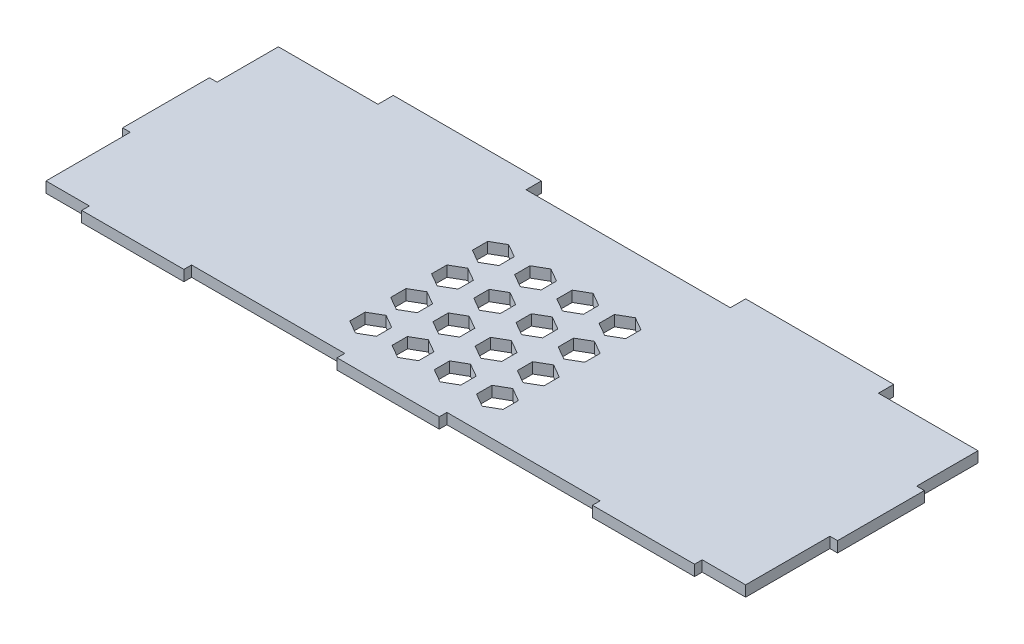
SolidWorks part; units mm, degrees
ref_plane "Front Plane" through (0, 0, 0) normal (0, 0, 1) x (1, 0, 0)
ref_plane "Top Plane" through (0, 0, 0) normal (0, 1, 0) x (1, 0, 0)
ref_plane "Right Plane" through (0, 0, 0) normal (1, 0, 0) x (0, 0, -1)
sketch "Sketch2" plane through (0, 0, 0) normal (0, 1, 0) x (1, 0, 0)
  line L5 (-70, 23.5) -> (-49, 23.5)
  line L6 (70, -23.5) -> (-70, -23.5)
  line L15 (70, -23.5) -> (70, 23.5)
  line L17 (-70, -23.5) -> (-70, 23.5)
  line L18 (70, -23.5) -> (-70, 23.5) construction
  line L19 (70, 23.5) -> (-70, -23.5) construction
  line L20 (-49, 23.5) -> (-49, 26.5)
  line L21 (-49, 26.5) -> (-20, 26.5)
  line L22 (-20, 26.5) -> (-20, 23.5)
  line L24 (20, 23.5) -> (20, 26.5)
  line L25 (20, 26.5) -> (49, 26.5)
  line L26 (49, 26.5) -> (49, 23.5)
  line L27 (49, 23.5) -> (70, 23.5)
  line L28 (-20, 23.5) -> (20, 23.5)
  point P0 (0, 0)
  dimension "D1" = 140
  dimension "D2" = 47
  dimension "D3" = 140
  dimension "D4" = 21
  dimension "D5" = 29
  dimension "D6" = 29
  dimension "D7" = 21
  dimension "D8" = 40
  dimension "D9" = 3
  dimension "D10" = 3
  dimension "D11" = 47
extrude "Boss-Extrude1" add sketch "Sketch2" along normal blind 2.1
sketch "Sketch5" plane through (0, 2.1, 0) normal (0, 1, 0) x (1, 0, 0)
  line L0 (-4.134, -11.5) -> (-6.7321, -13)
  line L1 (-12.4019, -11.5) -> (-15, -13)
  line L2 (-15, -13) -> (-15, -16)
  line L3 (-15, -16) -> (-12.4019, -17.5)
  line L4 (-12.4019, -17.5) -> (-9.8038, -16)
  line L5 (-9.8038, -16) -> (-9.8038, -13)
  line L6 (-9.8038, -13) -> (-12.4019, -11.5)
  line L7 (-6.7321, -13) -> (-6.7321, -16)
  line L8 (-6.7321, -16) -> (-4.134, -17.5)
  line L9 (-4.134, -17.5) -> (-1.5359, -16)
  line L10 (-1.5359, -16) -> (-1.5359, -13)
  line L11 (-1.5359, -13) -> (-4.134, -11.5)
  line L12 (4.134, -11.5) -> (1.5359, -13)
  line L13 (1.5359, -13) -> (1.5359, -16)
  line L14 (1.5359, -16) -> (4.134, -17.5)
  line L15 (4.134, -17.5) -> (6.7321, -16)
  line L16 (6.7321, -16) -> (6.7321, -13)
  line L17 (6.7321, -13) -> (4.134, -11.5)
  line L18 (12.4019, -11.5) -> (9.8038, -13)
  line L19 (9.8038, -13) -> (9.8038, -16)
  line L20 (9.8038, -16) -> (12.4019, -17.5)
  line L21 (12.4019, -17.5) -> (15, -16)
  line L22 (15, -16) -> (15, -13)
  line L23 (15, -13) -> (12.4019, -11.5)
  line L24 (-4.134, -3.5) -> (-6.7321, -5)
  line L25 (-6.7321, -5) -> (-6.7321, -8)
  line L26 (-6.7321, -8) -> (-4.134, -9.5)
  line L27 (-4.134, -9.5) -> (-1.5359, -8)
  line L28 (-1.5359, -8) -> (-1.5359, -5)
  line L29 (-1.5359, -5) -> (-4.134, -3.5)
  line L30 (4.134, -3.5) -> (1.5359, -5)
  line L31 (1.5359, -5) -> (1.5359, -8)
  line L32 (1.5359, -8) -> (4.134, -9.5)
  line L33 (4.134, -9.5) -> (6.7321, -8)
  line L34 (6.7321, -8) -> (6.7321, -5)
  line L35 (6.7321, -5) -> (4.134, -3.5)
  line L36 (12.4019, -3.5) -> (9.8038, -5)
  line L37 (9.8038, -5) -> (9.8038, -8)
  line L38 (9.8038, -8) -> (12.4019, -9.5)
  line L39 (12.4019, -9.5) -> (15, -8)
  line L40 (15, -8) -> (15, -5)
  line L41 (15, -5) -> (12.4019, -3.5)
  line L42 (-4.134, 4.5) -> (-6.7321, 3)
  line L43 (-6.7321, 3) -> (-6.7321, 0)
  line L44 (-6.7321, 0) -> (-4.134, -1.5)
  line L45 (-4.134, -1.5) -> (-1.5359, 0)
  line L46 (-1.5359, 0) -> (-1.5359, 3)
  line L47 (-1.5359, 3) -> (-4.134, 4.5)
  line L48 (4.134, 4.5) -> (1.5359, 3)
  line L49 (1.5359, 3) -> (1.5359, 0)
  line L50 (1.5359, 0) -> (4.134, -1.5)
  line L51 (4.134, -1.5) -> (6.7321, 0)
  line L52 (6.7321, 0) -> (6.7321, 3)
  line L53 (6.7321, 3) -> (4.134, 4.5)
  line L54 (12.4019, 4.5) -> (9.8038, 3)
  line L55 (9.8038, 3) -> (9.8038, 0)
  line L56 (9.8038, 0) -> (12.4019, -1.5)
  line L57 (12.4019, -1.5) -> (15, 0)
  line L58 (15, 0) -> (15, 3)
  line L59 (15, 3) -> (12.4019, 4.5)
  line L60 (-4.134, 12.5) -> (-6.7321, 11)
  line L61 (-6.7321, 11) -> (-6.7321, 8)
  line L62 (-6.7321, 8) -> (-4.134, 6.5)
  line L63 (-4.134, 6.5) -> (-1.5359, 8)
  line L64 (-1.5359, 8) -> (-1.5359, 11)
  line L65 (-1.5359, 11) -> (-4.134, 12.5)
  line L66 (4.134, 12.5) -> (1.5359, 11)
  line L67 (1.5359, 11) -> (1.5359, 8)
  line L68 (1.5359, 8) -> (4.134, 6.5)
  line L69 (4.134, 6.5) -> (6.7321, 8)
  line L70 (6.7321, 8) -> (6.7321, 11)
  line L71 (6.7321, 11) -> (4.134, 12.5)
  line L72 (12.4019, 12.5) -> (9.8038, 11)
  line L73 (9.8038, 11) -> (9.8038, 8)
  line L74 (9.8038, 8) -> (12.4019, 6.5)
  line L75 (12.4019, 6.5) -> (15, 8)
  line L76 (15, 8) -> (15, 11)
  line L77 (15, 11) -> (12.4019, 12.5)
  line L78 (-12.4019, -3.5) -> (-15, -5)
  line L79 (-15, -5) -> (-15, -8)
  line L80 (-15, -8) -> (-12.4019, -9.5)
  line L81 (-12.4019, -9.5) -> (-9.8038, -8)
  line L82 (-9.8038, -8) -> (-9.8038, -5)
  line L83 (-9.8038, -5) -> (-12.4019, -3.5)
  line L84 (-12.4019, 4.5) -> (-15, 3)
  line L85 (-15, 3) -> (-15, 0)
  line L86 (-15, 0) -> (-12.4019, -1.5)
  line L87 (-12.4019, -1.5) -> (-9.8038, 0)
  line L88 (-9.8038, 0) -> (-9.8038, 3)
  line L89 (-9.8038, 3) -> (-12.4019, 4.5)
  line L90 (-12.4019, 12.5) -> (-15, 11)
  line L91 (-15, 11) -> (-15, 8)
  line L92 (-15, 8) -> (-12.4019, 6.5)
  line L93 (-12.4019, 6.5) -> (-9.8038, 8)
  line L94 (-9.8038, 8) -> (-9.8038, 11)
  line L95 (-9.8038, 11) -> (-12.4019, 12.5)
  line L99 (20, 23.5) -> (-20, 23.5) construction
  line L100 (-70, 23.5) -> (-70, -23.5) construction
  line L101 (70, -23.5) -> (70, 23.5) construction
  circle A0 centre (-12.4019, -14.5) radius 2.5981 construction
  dimension "D1" = 3
  dimension "D4" = 55
  dimension "D5" = 55
  dimension "D6" = 14.5
  dimension "D7" = 8
  dimension "D8" = 11
  dimension "D2" = 4
  dimension "D3" = 4
extrude "Cut-Extrude1" cut sketch "Sketch5" against normal through all
sketch "Sketch6" plane through (0, 2.1, 0) normal (0, 1, 0) x (1, 0, 0)
  line L0 (70, 23.5) -> (68.5, 23.5)
  line L1 (70, 23.5) -> (49, 23.5) construction
  line L2 (68.5, 23.5) -> (68.5, 11.5)
  line L4 (70, -23.5) -> (70, 23.5) construction
  line L9 (70, 11.5) -> (70, 23.5)
  line L10 (68.5, -5.5) -> (68.5, -23.5)
  line L11 (-70, -23.5) -> (70, -23.5) construction
  line L12 (68.5, -23.5) -> (70, -23.5)
  line L13 (70, -23.5) -> (70, -5.5)
  line L14 (70, -23.5) -> (70, -22)
  line L15 (70, -22) -> (60, -22)
  line L16 (60, -22) -> (60, -23.5)
  line L17 (60, -23.5) -> (70, -23.5)
  line L18 (40, -23.5) -> (40, -22)
  line L19 (40, -22) -> (10, -22)
  line L20 (10, -22) -> (10, -23.5)
  line L21 (10, -23.5) -> (40, -23.5)
  line L22 (-10, -23.5) -> (-10, -22)
  line L23 (-10, -22) -> (-40, -22)
  line L24 (-40, -22) -> (-40, -23.5)
  line L25 (-40, -23.5) -> (-10, -23.5)
  line L26 (-70, 23.5) -> (-68.5, 23.5)
  line L27 (-49, 23.5) -> (-70, 23.5) construction
  line L28 (-68.5, 23.5) -> (-68.5, 11.5)
  line L29 (-68.5, 11.5) -> (-70, 11.5)
  line L30 (-70, 23.5) -> (-70, -23.5) construction
  line L31 (-70, 11.5) -> (-70, 23.5)
  line L32 (-70, -5.5) -> (-68.5, -5.5)
  line L33 (-68.5, -5.5) -> (-68.5, -23.5)
  line L34 (-68.5, -23.5) -> (-70, -23.5)
  line L35 (-70, -23.5) -> (-70, -5.5)
  line L36 (-70, -23.5) -> (-60, -23.5)
  line L37 (-60, -23.5) -> (-60, -22)
  line L38 (-60, -22) -> (-70, -22)
  line L39 (-70, -22) -> (-70, -23.5)
  line L40 (68.5, -5.5) -> (70, -5.5)
  line L41 (70, 11.5) -> (68.5, 11.5)
  dimension "D1" = 1.5
  dimension "D2" = 12
  dimension "D3" = 1.5
  dimension "D4" = 18
  dimension "D5" = 10
  dimension "D6" = 1.5
  dimension "D7" = 1.5
  dimension "D8" = 12
  dimension "D9" = 1.5
  dimension "D10" = 18
  dimension "D11" = 10
  dimension "D12" = 1.5
  dimension "D13" = 30
  dimension "D14" = 30
  dimension "D15" = 20
  dimension "D16" = 20
  dimension "D17" = 1.5
  dimension "D18" = 1.5
extrude "Cut-Extrude2" cut sketch "Sketch6" against normal through all contours L41 L9 L0 L2 | L20 L21 L18 L19 | L16 L17 L10 L15 | L37 L38 L33 L36 | L38 L33 L32 L35 | L33 L38 L35 L34 | L31 L26 L28 L29 | L13 L40 L10 L12 | L23 L24 L25 L22 region at (69.25, 2.1, -17.5) region at (64.25, 2.1, 22.75) region at (25, 2.1, 22.75) region at (-69.25, 2.1, 13.75) region at (-69.25, 2.1, 22.75) region at (-64.25, 2.1, 22.75)
